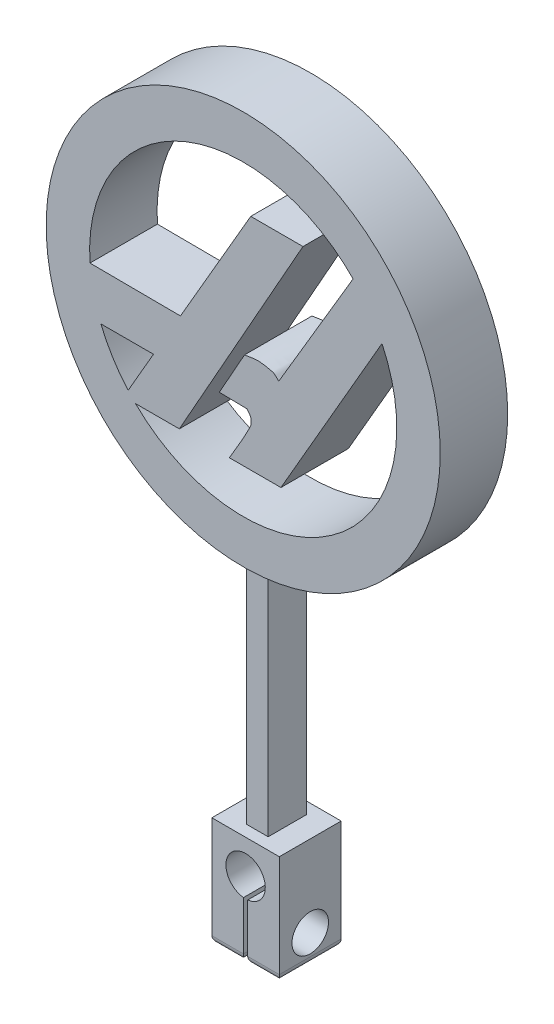
SolidWorks part; units mm, degrees
ref_plane "Front Plane" through (0, 0, 0) normal (0, 0, 1) x (1, 0, 0)
ref_plane "Top Plane" through (0, 0, 0) normal (0, 1, 0) x (1, 0, 0)
ref_plane "Right Plane" through (0, 0, 0) normal (1, 0, 0) x (0, 0, -1)
ref_axis "MotorAxis" through (0, 0, 11.2732) along (0, 0, -1)
sketch "Sketch1" plane through (0, 0, 0) normal (0, 0, 1) x (1, 0, 0)
  line L0 (-2.4, 2.4) -> (2.4, 2.4)
  line L1 (-2.4, -5.37) -> (2.4, -5.37)
  line L2 (2.4, 2.4) -> (2.4, -5.37)
  line L3 (-2.4, 2.4) -> (-2.4, -5.37)
  circle A0 centre (0, 0) radius 1.4 construction
extrude "Joint" add sketch "Sketch1" against normal blind 2.2 and the other way blind 2.2
sketch "Sketch2" plane through (0, 0, 0) normal (0, 1, 0) x (1, 0, 0)
  line L0 (-2.4, 0) -> (2.4, 0) construction
  line L1 (-2.4, -2.2) -> (-2.4, 2.2) construction
  line L2 (2.4, -2.2) -> (2.4, 2.2) construction
  line L3 (0.775, 1.37) -> (-0.775, 1.37)
  line L4 (0.775, -1.37) -> (0.775, 1.37)
  line L5 (0.775, -1.37) -> (-0.775, -1.37)
  line L6 (-0.775, 1.37) -> (-0.775, -1.37)
extrude "Arm" add sketch "Sketch2" along normal blind 19.2
sketch "Sketch3" plane through (0, 0, 0) normal (0, 0, 1) x (1, 0, 0)
  line L0 (0, -2.42) -> (0, 2.42) construction
  circle A0 centre (0, 0) radius 1.4
sketch "Sketch4" plane through (0, 0, 0) normal (1, 0, 0) x (0, 0, -1)
  circle A1 centre (0, -3.385) radius 1.3
extrude "MotShaft" cut sketch "Sketch3" against normal blind 2.2 and the other way blind 2.2
extrude "Bolt" cut sketch "Sketch4" against normal blind 2.4 and the other way blind 2.4
sketch "Sketch5" plane through (0, 0, 0) normal (0, 0, 1) x (1, 0, 0)
  line L0 (0, 0) -> (0, -5.37) construction
  line L2 (-2.4, -5.37) -> (2.4, -5.37) construction
  line L3 (-0.15, -0.6199) -> (0.15, -0.6199)
  line L4 (0.15, -0.6199) -> (0.15, -5.37)
  line L5 (-0.15, -0.6199) -> (-0.15, -5.37)
  line L6 (0.15, -5.37) -> (-0.15, -5.37)
  point P9 (0, -0.6199)
extrude "Slot" cut sketch "Sketch5" against normal blind 2.4 and the other way blind 2.4
sketch "Sketch6" plane through (0, 0, 0) normal (0, 0, 1) x (1, 0, 0)
  line L3 (7.8507, 40.8412) -> (2.5633, 31.8933)
  line L4 (0.1233, 32.2933) -> (-1.6706, 29.0933)
  line L5 (-1.6706, 29.0933) -> (0.2833, 29.0533)
  line L6 (-0.9567, 25.4133) -> (2.7147, 25.4133)
  line L7 (2.7147, 25.4133) -> (9.9076, 37.8848)
  line L8 (-7.6368, 25.4121) -> (-4.5167, 25.4133)
  line L9 (-4.5167, 25.4133) -> (4.2833, 41.0533)
  line L10 (4.2833, 41.0533) -> (0.5665, 41.0533)
  line L11 (0.5665, 41.0533) -> (-4.4367, 32.4133)
  line L12 (-4.4367, 32.4133) -> (-10.8767, 32.4533)
  line L13 (-10.0997, 29.0933) -> (-6.3567, 29.0933)
  line L14 (-6.3567, 29.0933) -> (-8.1613, 25.9653)
  arc A1 (-10.0997, 29.0933) -> (-8.1613, 25.9653) centre (0.0287, 33.2052) ccw
  arc A2 (-7.6368, 25.4121) -> (9.9076, 37.8848) centre (0.0287, 33.2052) ccw
  arc A3 (7.8507, 40.8412) -> (-10.8767, 32.4533) centre (0.0287, 33.2052) ccw
  circle A4 centre (0.0287, 33.2052) radius 14.0251
  spline S0 degree 3 poles (2.5633, 31.8933) (2.4033, 32.0133) (2.2776, 32.2057) (2.0833, 32.2533) (1.0951, 32.4953) (0.8774, 32.419) (0.1233, 32.2933) knots 0 0 0 0 1 1 1 2 2 2 2
  spline S1 degree 3 poles (0.2833, 29.0533) (0.3766, 28.92) (0.5253, 28.8116) (0.5633, 28.6533) (0.6101, 28.4584) (0.6084, 28.2348) (0.5233, 28.0533) (0.0948, 27.14) (-0.4634, 26.2933) (-0.9567, 25.4133) knots 0 0 0 0 1 1 1 2 2 2 3 3 3 3
  point P0 (0.775, 19.2)
  point P1 (0, 0)
extrude "Logo" add sketch "Sketch6" along normal blind 2.4 and the other way blind 2.4
ref_axis "Axis1" through (0.1233, 32.2933, 2.4) along (0, 0, 1)
fillet "Fillet2" radius 0.5 8 edges at (-1.275, -5.37, -2.2) (-2.4, -5.37, 0) (-1.275, -5.37, 2.2) (-0.15, -5.37, 0) (1.275, -5.37, 2.2) (2.4, -5.37, 0) (1.275, -5.37, -2.2) (0.15, -5.37, 0)
